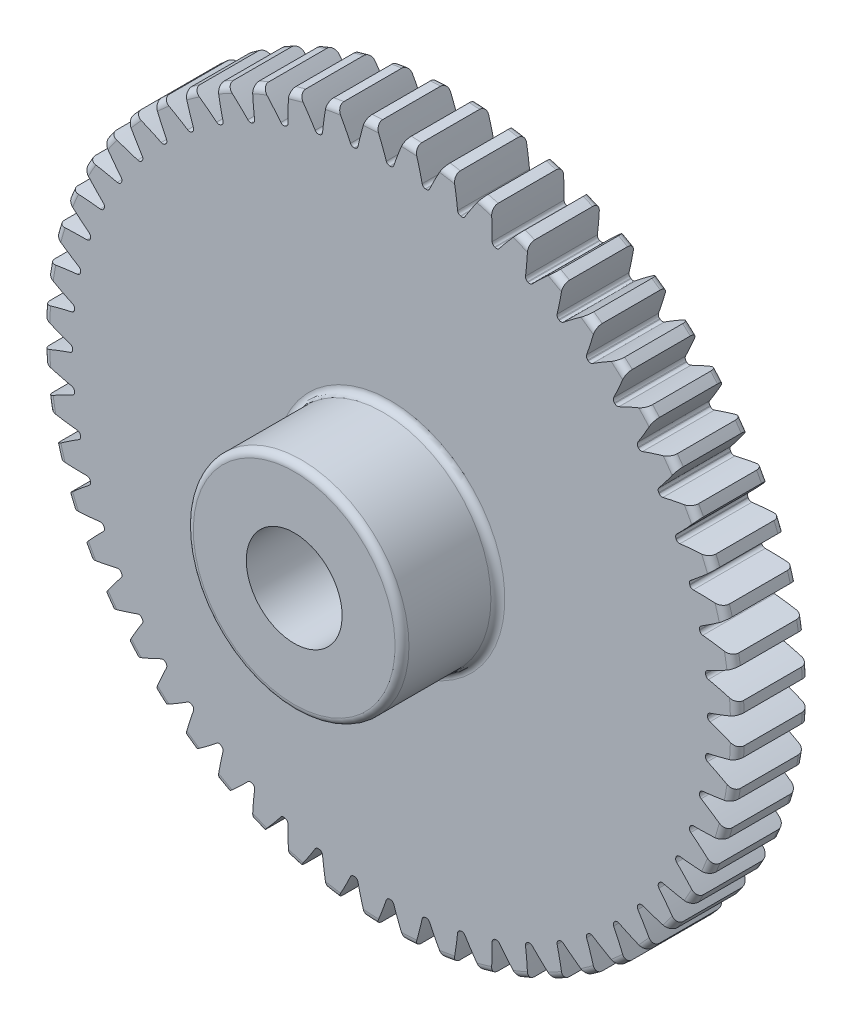
SolidWorks part; units mm, degrees
ref_plane "Front Plane" through (0, 0, 0) normal (0, 0, 1) x (1, 0, 0)
ref_plane "Top Plane" through (0, 0, 0) normal (0, 1, 0) x (1, 0, 0)
ref_plane "Right Plane" through (0, 0, 0) normal (1, 0, 0) x (0, 0, -1)
sketch "Sketch1" plane through (0, 0, 0) normal (0, 0, 1) x (1, 0, 0)
  line L0 (-711.2, 0) -> (711.2, 0) construction
  circle A0 centre (0, 0) radius 29 construction
  circle A1 centre (0, 0) radius 28 construction
  circle A2 centre (0, 0) radius 26.5 construction
  circle A3 centre (0, 0) radius 9 construction
  circle A4 centre (0, 0) radius 4 construction
  dimension "D1" = 2.5
  dimension "OD" = 58
  dimension "Pitch Dia." = 56
  dimension "D2" = 1
  dimension "D3" = 2.5
  dimension "Root Dia." = 53
  dimension "Hub Dia." = 18
  dimension "Shaft Dia." = 8
  dimension "Number of Teeth" = 1422.4
sketch "Sketch2" plane through (0, 0, 0) normal (1, 0, 0) x (0, 0, -1)
  line L0 (0, 0) -> (-6, 0) construction
  line L1 (-6, 0) -> (-14, 0) construction
  dimension "Overall Width" = 14
  dimension "Face Width" = 6
sketch "Sketch4" plane through (0, 0, 0) normal (1, 0, 0) x (0, 0, -1)
  line L0 (-14, 4) -> (-14, 9)
  line L1 (-14, 9) -> (-6, 9)
  line L2 (-6, 9) -> (-6, 29)
  line L3 (-6, 29) -> (0, 29)
  line L4 (0, 29) -> (0, 4)
  line L5 (-6, 9) -> (-6, 0) construction
  line L6 (0, 29) -> (0, -29) construction
  line L7 (-6, 9) -> (0, 9) construction
  line L12 (-14, 4) -> (0, 4)
revolve "Revolve1" add sketch "Sketch4" angle 360 about L1
fillet "Fillet2" radius 0.58 4 edges at (0, 9, 14) (0, 9, 6) (0, 29, 6) (0, 29, 0)
sketch "Sketch7" plane through (0, 0, 6) normal (0, 0, 1) x (1, 0, 0)
  line L0 (0, 0) -> (0, 29) construction
  line L1 (0.7853, 27.989) -> (1.1763, 28.9761) construction
  line L3 (1.626, 28.9544) -> (1.57, 27.956) construction
  line L4 (1.57, 27.956) -> (1.4859, 26.4583) construction
  line L5 (0, 0) -> (1.4859, 26.4583) construction
  line L6 (0.7853, 27.989) -> (0, 0) construction
  line L7 (0.7853, 27.989) -> (0.8133, 28.9886) construction
  line L8 (0.7853, 27.989) -> (0, 0) construction
  circle A0 centre (0, 0) radius 29 construction
  arc A1 (-0.0278, 26.5) -> (0.0278, 26.5) centre (0, 0) cw
  circle A2 centre (0, 0) radius 26.5 construction
  arc A3 (-0.7853, 27.989) -> (0.7853, 27.989) centre (0, 0) cw construction
  circle A4 centre (0, 0) radius 28 construction
  arc A5 (2.0538, 28.9272) -> (1.1979, 28.9752) centre (0, 0) ccw construction
  arc A6 (0.7853, 27.989) -> (2.3534, 27.9009) centre (0, 0) cw construction
  arc A7 (-1.1979, 28.9752) -> (1.1979, 28.9752) centre (0, 0) cw
  arc A8 (0.3121, 26.7033) -> (1.1979, 28.9752) centre (26.8178, 17.6783) cw
  arc A9 (-0.3121, 26.7033) -> (-1.1979, 28.9752) centre (-26.8178, 17.6783) ccw
  arc A10 (-0.0278, 26.5) -> (-0.3121, 26.7033) centre (-0.0281, 26.8) cw
  arc A11 (0.0278, 26.5) -> (0.3121, 26.7033) centre (0.0281, 26.8) ccw
  point P26 (-0.2434, 26.4989)
  point P29 (0.2434, 26.4989)
  dimension "D4" = 0.3
  dimension "D5" = 28
  dimension "D2" = 1.5708
  dimension "D1" = 3.1416
  dimension "D3" = 20
extrude "Cut-Extrude2" cut sketch "Sketch7" against normal through all
pattern_circular "CirPattern1" count 56 over 360 about axis through (0, 0, 14) along (0, 0, -1) of "Cut-Extrude2"
equation "\"D1@Sketch1\"=2.5*(\"Pitch Dia.@Sketch1\"/\"Number of Teeth@Sketch1\")"
equation "\"D1@CirPattern1\"=\"Number of Teeth@Sketch1\""
equation "\"D1@Fillet2\"=\"OD@Sketch1\"*.01"
equation "\"D1@Sketch7\"=3.14159*(\"Pitch Dia.@Sketch1\"/\"Number of Teeth@Sketch1\")"
equation "\"D2@Sketch7\"=\"D1@Sketch7\"/2"
equation "\"D4@Sketch7\"=\"D1@Sketch7\"*.0955"
equation "\"D5@Sketch7\"=\"Pitch Dia.@Sketch1\"/2"
